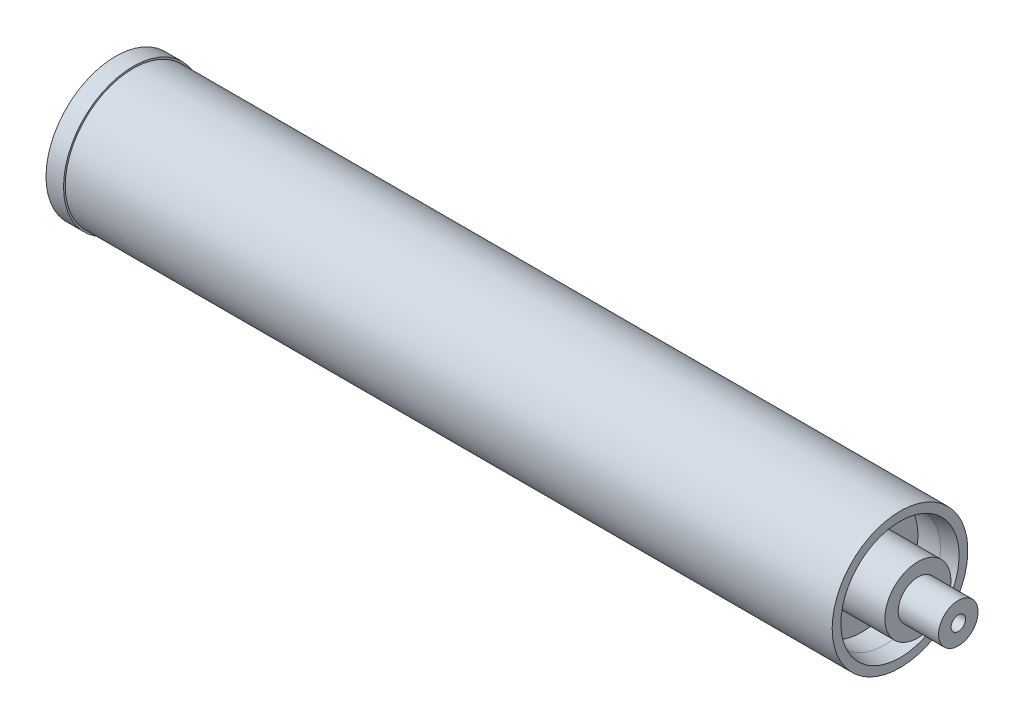
SolidWorks part; units mm, degrees
ref_plane "Plan de face" through (0, 0, 0) normal (0, 0, 1) x (1, 0, 0)
ref_plane "Plan de dessus" through (0, 0, 0) normal (0, 1, 0) x (1, 0, 0)
ref_plane "Plan de droite" through (0, 0, 0) normal (1, 0, 0) x (0, 0, -1)
sketch "Esquisse2" plane through (0, 0, 0) normal (0, 0, 1) x (1, 0, 0)
  line L0 (0, 0) -> (97.8436, 0) construction
  line L1 (0, -26) -> (0, 26) construction
  line L2 (0, 26) -> (12.7, 26)
  line L3 (12.7, 26) -> (12.7, 50.419) construction
  line L4 (12.7, 50.419) -> (25.4, 50.419)
  line L5 (25.4, 50.419) -> (25.4, 49.149)
  line L6 (25.4, 49.149) -> (581.02, 49.149)
  line L7 (581.02, 49.149) -> (581.02, 42.8202)
  line L8 (581.02, 42.8202) -> (569.6971, 40.5731)
  line L9 (569.6971, 40.5731) -> (553.412, 40.5731)
  line L10 (553.412, 40.5731) -> (553.412, 23.9395)
  line L11 (553.412, 23.9395) -> (593.98, 23.9395)
  line L12 (593.98, 23.9395) -> (593.98, 14.2875)
  line L13 (593.98, 14.2875) -> (623.27, 14.2875)
  line L14 (623.27, 14.2875) -> (623.27, -14.2875) construction
  line L15 (623.27, 0) -> (0, 0) construction
  line L16 (593.98, -14.2875) -> (623.27, -14.2875) construction
  line L17 (593.98, -23.9395) -> (593.98, -14.2875) construction
  line L18 (553.412, -23.9395) -> (593.98, -23.9395) construction
  line L19 (553.412, -40.5731) -> (553.412, -23.9395) construction
  line L20 (569.6971, -40.5731) -> (553.412, -40.5731) construction
  line L21 (581.02, -42.8202) -> (569.6971, -40.5731) construction
  line L22 (581.02, -49.149) -> (581.02, -42.8202) construction
  line L23 (25.4, -49.149) -> (581.02, -49.149) construction
  line L24 (25.4, -50.419) -> (25.4, -49.149) construction
  line L25 (12.7, -50.419) -> (25.4, -50.419) construction
  line L26 (12.7, -26) -> (12.7, -50.419) construction
  line L27 (0, -26) -> (12.7, -26) construction
  line L28 (12.7, 50.419) -> (12.7, 38.2095)
  line L29 (12.7, 38.2095) -> (25.4, 35.6891)
  line L30 (25.4, 35.6891) -> (36.5674, 35.6891)
  line L31 (36.5674, 35.6891) -> (36.5674, 26)
  line L32 (36.5674, 26) -> (12.7, 26)
  line L33 (25.4, 35.6891) -> (25.4, 49.149) construction
  line L34 (36.5674, -26) -> (12.7, -26) construction
  line L35 (36.5674, -35.6891) -> (36.5674, -26) construction
  line L36 (25.4, -35.6891) -> (36.5674, -35.6891) construction
  line L37 (12.7, -38.2095) -> (25.4, -35.6891) construction
  line L38 (12.7, -50.419) -> (12.7, -38.2095) construction
  line L39 (0, 26) -> (0, 0)
  line L40 (0, 0) -> (623.27, 0)
  line L41 (623.27, 0) -> (623.27, 14.2875)
  dimension "D2" = 555.62
  dimension "D3" = 568.58
  dimension "D4" = 28.575
  dimension "D5" = 47.879
  dimension "D6" = 98.298
  dimension "D7" = 12.7
  dimension "D8" = 100.838
  dimension "D9" = 12.7
  dimension "D10" = 52
  dimension "D11" = 597.87
revolve "Révolution7" add sketch "Esquisse2" angle 360 about L0
sketch "Esquisse3" plane through (0, 0, 0) normal (0, 0, 1) x (1, 0, 0)
  line L0 (0, 0) -> (623.27, 0) construction
  line L1 (623.27, -14.2875) -> (623.27, 14.2875) construction
  line L2 (0, 20) -> (0, 0)
  line L3 (0, 26) -> (0, -26) construction
  line L4 (0, 0) -> (549.0647, 0)
  line L7 (549.0647, 0) -> (588.426, 0)
  line L8 (549.0647, 15.2835) -> (549.0647, 44.271)
  line L9 (549.0647, 44.271) -> (65.8719, 44.271)
  line L10 (65.8719, 44.271) -> (34.083, 14.3276)
  line L11 (34.083, 14.3276) -> (19.083, 14.3276)
  line L12 (19.083, 14.3276) -> (0, 20)
  line L13 (36.5674, 26) -> (0, 26) construction
  line L16 (549.0647, 15.2835) -> (588.426, 15.2835)
  line L17 (588.426, 0) -> (588.426, 15.2835)
  line L18 (623.27, 0) -> (600.9481, 0)
  line L19 (623.27, 0) -> (623.27, 5.2367)
  line L20 (623.27, 5.2367) -> (600.9481, 5.2367)
  line L21 (600.9481, 0) -> (600.9481, 5.2367)
  dimension "D1" = 15
  dimension "D2" = 6
revolve "Enlèvement de matière-Révolution1" cut sketch "Esquisse3" angle 360 about L0
